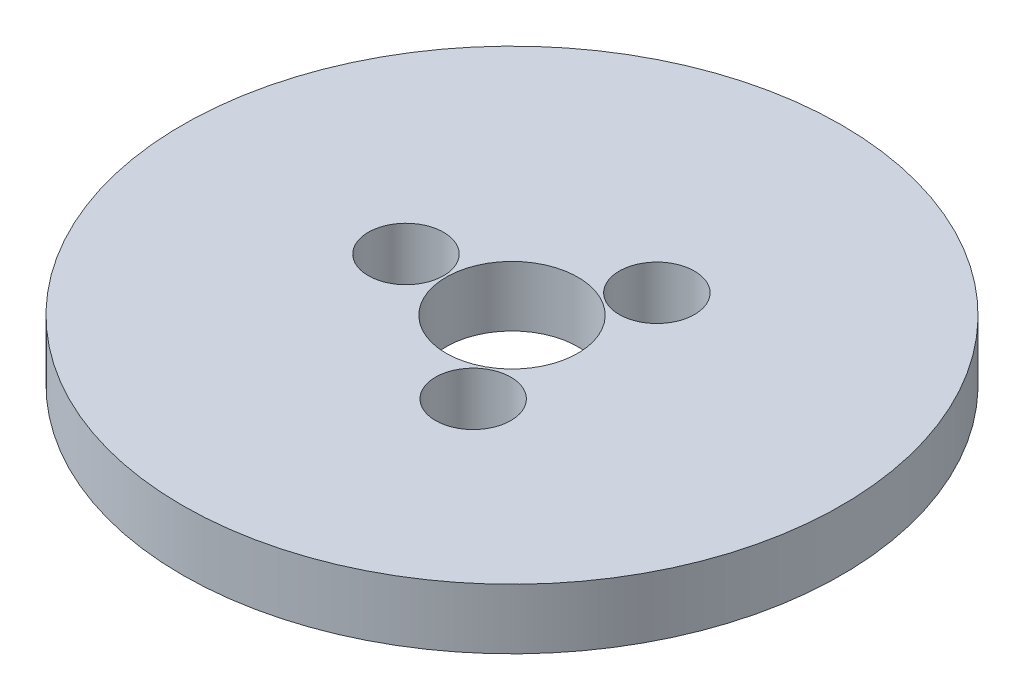
SolidWorks part; units mm, degrees
ref_plane "Front Plane" through (0, 0, 0) normal (0, 0, 1) x (1, 0, 0)
ref_plane "Top Plane" through (0, 0, 0) normal (0, 1, 0) x (1, 0, 0)
ref_plane "Right Plane" through (0, 0, 0) normal (1, 0, 0) x (0, 0, -1)
sketch "Sketch1" plane through (0, 0, 0) normal (0, 1, 0) x (1, 0, 0)
  circle A0 centre (0, 0) radius 87.5
  dimension "FLANGE_OD" = 175
extrude "Boss-Extrude1" add sketch "Sketch1" along normal blind 16
sketch "Sketch2" plane through (0, 0, 0) normal (0, 1, 0) x (1, 0, 0)
  circle A0 centre (0, 0) radius 17.5
  dimension "BORE_D" = 35
extrude "Cut-Extrude1" cut sketch "Sketch2" along normal through all
sketch "Sketch3" plane through (0, 16, 0) normal (0, 1, 0) x (1, 0, 0)
  circle A0 centre (0, 0) radius 28.1575 construction
  circle A1 centre (-28.1575, 0) radius 10
  dimension "BOLT_D" = 20
  dimension "BOLT_PCD" = 56.3151
extrude "Cut-Extrude2" cut sketch "Sketch3" against normal blind 14.6542
pattern_circular "CirPattern1" count 3 over 360 about axis through (0, 0, 0) along (0, 1, 0) of "Cut-Extrude2"
